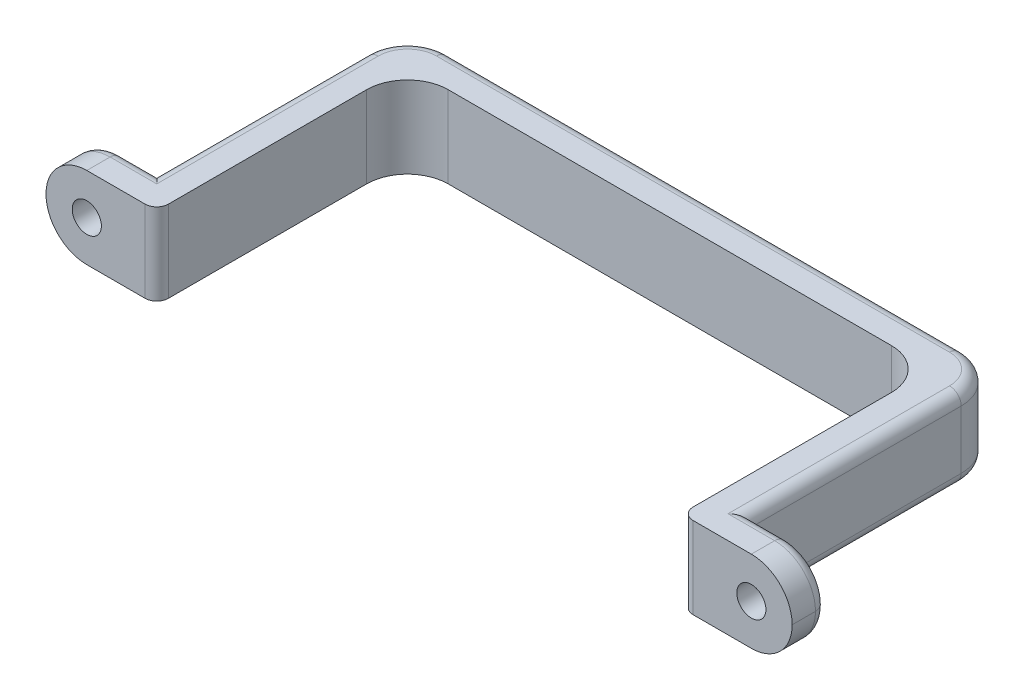
SolidWorks part; units mm, degrees
ref_plane "Спереди" through (0, 0, 0) normal (0, 0, 1) x (1, 0, 0)
ref_plane "Сверху" through (0, 0, 0) normal (0, 1, 0) x (1, 0, 0)
ref_plane "Справа" through (0, 0, 0) normal (1, 0, 0) x (0, 0, -1)
sketch "Эскиз1" plane through (0, 0, 0) normal (0, 1, 0) x (1, 0, 0)
  line L0 (54.5, 24.5) -> (54.5, 21.5)
  line L7 (0, 0) -> (6.5, 0)
  line L8 (0, 0) -> (0, 3)
  line L9 (0, 3) -> (6.5, 3)
  line L10 (6.5, 0) -> (6.5, 3)
  line L11 (6.5, 0) -> (9.5, 0)
  line L12 (6.5, 0) -> (6.5, 24.5)
  line L13 (6.5, 24.5) -> (9.5, 24.5)
  line L14 (9.5, 0) -> (9.5, 24.5)
  line L15 (9.5, 24.5) -> (54.5, 24.5)
  line L16 (9.5, 24.5) -> (9.5, 21.5)
  line L17 (9.5, 21.5) -> (54.5, 21.5)
  line L18 (32, 24.5) -> (32, 21.5)
  line L19 (54.5, 0) -> (54.5, 24.5)
  line L20 (57.5, 24.5) -> (54.5, 24.5)
  line L21 (57.5, 0) -> (57.5, 24.5)
  line L22 (57.5, 0) -> (54.5, 0)
  line L23 (57.5, 0) -> (57.5, 3)
  line L24 (64, 3) -> (57.5, 3)
  line L25 (64, 0) -> (64, 3)
  line L26 (64, 0) -> (57.5, 0)
  dimension "D2" = 6.5
  dimension "D3" = 3
  dimension "D1" = 32
  dimension "D4" = 24.5
extrude "Бобышка-Вытянуть1" add sketch "Эскиз1" along normal blind 7 contours L7 L10 L9 L8 | L11 L14 L13 L12 L10 | L18 L15 L14 L17 | L15 L18 L17 L0 | L22 L21 L20 L0 L19 | L26 L25 L24 L21 region at (56, 0, -12.25) region at (43.25, 0, -23) region at (20.75, 0, -23) region at (8, 0, -12.25) region at (60.75, 0, -1.5) region at (3.25, 0, -1.5)
fillet "Скругление3" radius 3.5 8 edges at (64, 7, -1.5) (64, 0, -1.5) (0, 0, -1.5) (0, 7, -1.5) (57.5, 3.5, -24.5) (6.5, 3.5, -24.5) (54.5, 3.5, -21.5) (9.5, 3.5, -21.5)
sketch "Эскиз2" plane through (0, 0, 0) normal (0, 0, 1) x (1, 0, 0)
  circle A0 centre (3.5, 3.5) radius 1.25
  circle A1 centre (60.5, 3.5) radius 1.25
  dimension "D1" = 2.5
extrude "Вырез-Вытянуть1" cut sketch "Эскиз2" against normal up to next
fillet "Скругление4" radius 1 18 edges at (59, 0, -3) (62.9749, 1.0251, -3) (62.9749, 5.9749, -3) (5, 0, -3) (1.0251, 1.0251, -3) (1.0251, 5.9749, -3) (6.5, 0, -12) (7.5251, 0, -23.4749) (57.5, 0, -12) (56.4749, 0, -23.4749) (6.5, 7, -12) (7.5251, 7, -23.4749) (57.5, 7, -12) (56.4749, 7, -23.4749) (59, 7, -3) (5, 7, -3) (32, 0, -24.5) (32, 7, -24.5)
fillet "Скругление5" radius 1 2 edges at (54.5, 3.5, 0) (9.5, 3.5, 0)
